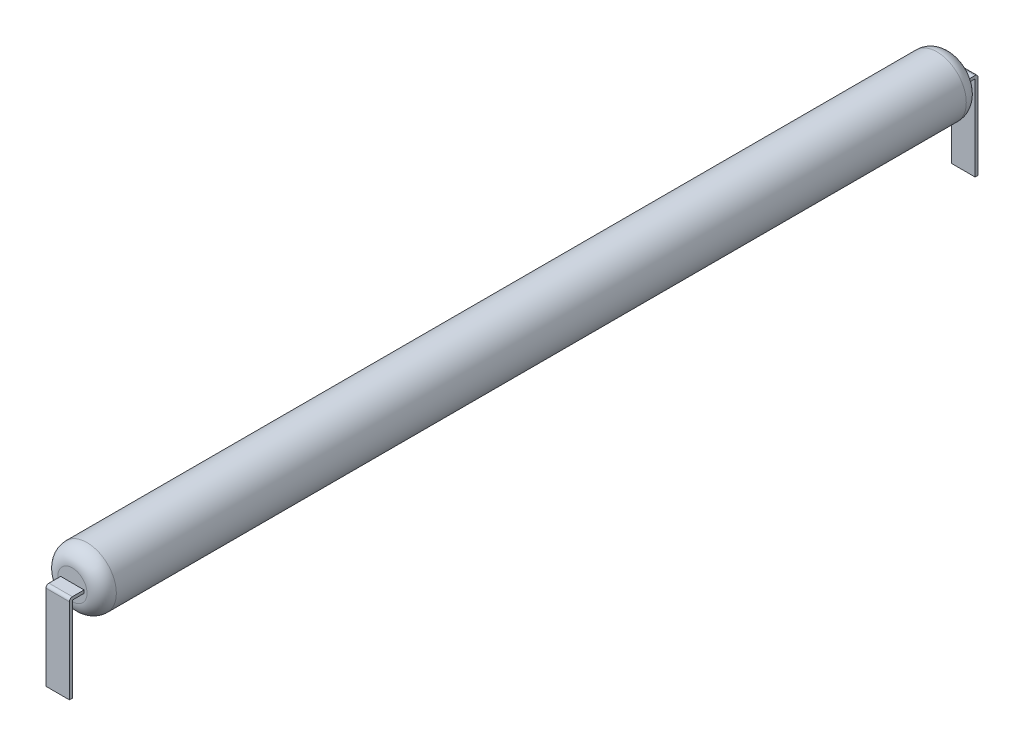
SolidWorks part; units mm, degrees
material "Plastique personnalisé"
ref_plane "Plan de face" through (0, 0, 0) normal (0, 0, 1) x (1, 0, 0)
ref_plane "Plan de dessus" through (0, 0, 0) normal (0, 1, 0) x (1, 0, 0)
ref_plane "Plan de droite" through (0, 0, 0) normal (1, 0, 0) x (0, 0, -1)
sketch "Esquisse1" plane through (0, 0, 0) normal (0, 0, 1) x (1, 0, 0)
  circle A0 centre (0, 0) radius 1
extrude "Boss.-Extru.1" add sketch "Esquisse1" along normal blind 15 and the other way blind 15
sketch "Esquisse2" plane through (0, 0, 15) normal (0, 0, 1) x (1, 0, 0)
  line L1 (-0.4, -0.05) -> (0.4, -0.05)
  line L2 (-0.4, -0.05) -> (-0.4, 0.05)
  line L3 (-0.4, 0.05) -> (0.4, 0.05)
  line L4 (0.4, -0.05) -> (0.4, 0.05)
  line L5 (-0.4, -0.05) -> (0.4, 0.05) construction
  line L6 (-0.4, 0.05) -> (0.4, -0.05) construction
  point P0 (0, 0)
  dimension "D1" = 0.8
  dimension "D2" = 0.1
extrude "Boss.-Extru.2" add sketch "Esquisse2" along normal blind 1
sketch "Esquisse3" plane through (0, 0, -15) normal (0, 0, -1) x (-1, 0, 0)
  line L1 (-0.4, -0.05) -> (0.4, -0.05)
  line L2 (-0.4, -0.05) -> (-0.4, 0.05)
  line L3 (-0.4, 0.05) -> (0.4, 0.05)
  line L4 (0.4, -0.05) -> (0.4, 0.05)
  line L5 (-0.4, -0.05) -> (0.4, 0.05) construction
  line L6 (-0.4, 0.05) -> (0.4, -0.05) construction
  point P0 (0, 0)
  dimension "D1" = 0.8
  dimension "D2" = 0.1
extrude "Boss.-Extru.3" add sketch "Esquisse3" along normal blind 1
fillet "Congé1" radius 0.5 2 edges at (1, 0, 15) (1, 0, -15)
sketch "Esquisse4" plane through (-0.4, 0, 0) normal (-1, 0, 0) x (0, 0, 1)
  line L0 (-15, 0.05) -> (-15.5, 0.05) construction
  line L1 (-16, 0.05) -> (-15, 0.05) construction
  line L2 (-15.5, 0.05) -> (-15.5, -2.95) construction
  line L4 (-15.5, -2.95) -> (-15.4, -2.95)
  line L5 (-15.5, -2.95) -> (-15.5, 0.05)
  line L6 (-15.5, 0.05) -> (-15.4, 0.05)
  line L7 (-15.4, -2.95) -> (-15.4, 0.05)
  dimension "D1" = 0.1
  dimension "D2" = 3
extrude "Boss.-Extru.4" add sketch "Esquisse4" against normal blind 0.8
sketch "Esquisse5" plane through (-0.4, 0, 0) normal (-1, 0, 0) x (0, 0, 1)
  line L1 (-16, 0.05) -> (-15.5, 0.05)
  line L2 (-16, 0.05) -> (-16, -0.05)
  line L3 (-16, -0.05) -> (-15.5, -0.05)
  line L4 (-15.5, 0.05) -> (-15.5, -0.05)
extrude "Enlèv. mat.-Extru.1" cut sketch "Esquisse5" against normal blind 0.8
fillet "Congé2" radius 0.1 1 edges at (0, 0.05, -15.5)
sketch "Esquisse6" plane through (-0.4, 0, 0) normal (-1, 0, 0) x (0, 0, 1)
  line L0 (15, 0.05) -> (15.5, 0.05) construction
  line L1 (16, 0.05) -> (15, 0.05) construction
  line L2 (15.5, 0.05) -> (15.5, -2.95) construction
  line L4 (15.5, -2.95) -> (15.4, -2.95)
  line L5 (15.5, -2.95) -> (15.5, 0.05)
  line L6 (15.5, 0.05) -> (15.4, 0.05)
  line L7 (15.4, -2.95) -> (15.4, 0.05)
  dimension "D1" = 0.1
  dimension "D2" = 3
extrude "Boss.-Extru.5" add sketch "Esquisse6" against normal blind 0.8
sketch "Esquisse7" plane through (-0.4, 0, 0) normal (-1, 0, 0) x (0, 0, 1)
  line L1 (16, 0.05) -> (15.5, 0.05)
  line L2 (16, 0.05) -> (16, -0.05)
  line L3 (16, -0.05) -> (15.5, -0.05)
  line L4 (15.5, 0.05) -> (15.5, -0.05)
extrude "Enlèv. mat.-Extru.2" cut sketch "Esquisse7" against normal blind 0.8
fillet "Congé3" radius 0.1 1 edges at (0, 0.05, 15.5)
